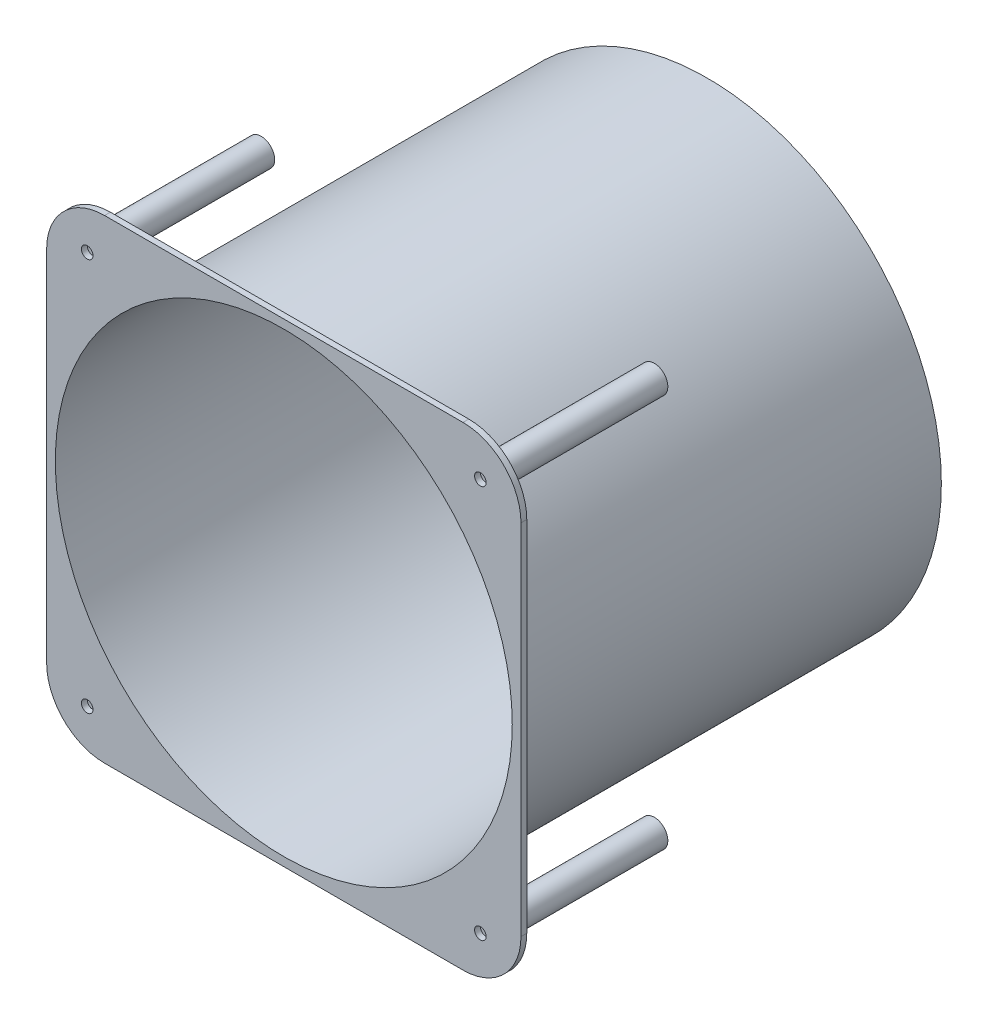
SolidWorks part; units mm, degrees
ref_plane "Front Plane" through (0, 0, 0) normal (0, 0, 1) x (1, 0, 0)
ref_plane "Top Plane" through (0, 0, 0) normal (0, 1, 0) x (1, 0, 0)
ref_plane "Right Plane" through (0, 0, 0) normal (1, 0, 0) x (0, 0, -1)
sketch "Sketch1" plane through (0, 0, 0) normal (0, 0, 1) x (1, 0, 0)
  circle A0 centre (0, 0) radius 51.308
  dimension "D1" = 102.616
extrude "Boss-Extrude1" add sketch "Sketch1" against normal blind 92.71
sketch "Sketch2" plane through (0, 0, 0) normal (0, 0, 1) x (1, 0, 0)
  line L1 (-51.943, -51.943) -> (51.943, -51.943)
  line L2 (-51.943, -51.943) -> (-51.943, 51.943)
  line L3 (-51.943, 51.943) -> (51.943, 51.943)
  line L4 (51.943, -51.943) -> (51.943, 51.943)
  line L5 (-51.943, -51.943) -> (51.943, 51.943) construction
  line L6 (-51.943, 51.943) -> (51.943, -51.943) construction
  circle A0 centre (43.053, 43.053) radius 1.27
  circle A1 centre (-43.053, 43.053) radius 1.27
  circle A2 centre (43.053, -43.053) radius 1.27
  circle A3 centre (-43.053, -43.053) radius 1.27
  point P0 (0, 0)
  dimension "D3" = 2.54
  dimension "D1" = 103.886
  dimension "D2" = 103.886
  dimension "D4" = 8.89
extrude "Boss-Extrude2" add sketch "Sketch2" against normal blind 1.27
shell "Shell1" thickness 1.27 removed face at (51.308, 0, -92.71) removed face at (-41.783, -43.053, 0)
fillet "Fillet1" radius 12.7 4 edges at (51.943, -51.943, -0.635) (-51.943, -51.943, -0.635) (-51.943, 51.943, -0.635) (51.943, 51.943, -0.635)
sketch "Sketch3" plane through (0, 0, -1.27) normal (0, 0, -1) x (-1, 0, 0)
  circle A0 centre (-43.053, 43.053) radius 2.9591
  circle A1 centre (43.053, 43.053) radius 2.9591
  circle A2 centre (43.053, -43.053) radius 2.9591
  circle A3 centre (-43.053, -43.053) radius 2.9591
  dimension "D1" = 5.9182
extrude "Boss-Extrude3" add sketch "Sketch3" along normal blind 36.83
